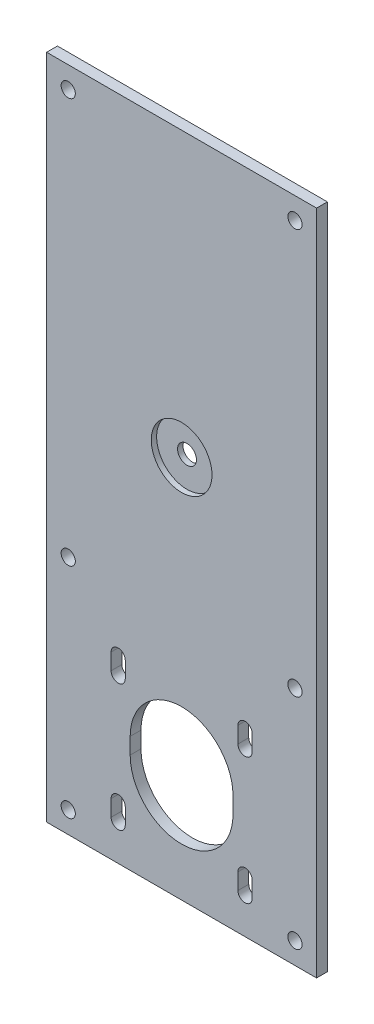
SolidWorks part; units mm, degrees
ref_plane "Front Plane" through (0, 0, 0) normal (0, 0, 1) x (1, 0, 0)
ref_plane "Top Plane" through (0, 0, 0) normal (0, 1, 0) x (1, 0, 0)
ref_plane "Right Plane" through (0, 0, 0) normal (1, 0, 0) x (0, 0, -1)
sketch "Sketch1" plane through (0, 0, 0) normal (0, 0, 1) x (1, 0, 0)
  line L1 (-50, 123.5) -> (50, 123.5)
  line L2 (-50, 123.5) -> (-50, -123.5)
  line L3 (-50, -123.5) -> (50, -123.5)
  line L4 (50, 123.5) -> (50, -123.5)
  line L5 (-50, 123.5) -> (50, -123.5) construction
  line L6 (-50, -123.5) -> (50, 123.5) construction
  line L8 (-19.05, -80.5) -> (-19.05, -86.5)
  line L9 (19.05, -86.5) -> (19.05, -80.5)
  line L10 (-23.5, -57) -> (-23.5, -63) construction
  line L14 (-20.87, -57) -> (-20.87, -63)
  line L15 (-26.13, -57) -> (-26.13, -63)
  line L16 (0, -83.5) -> (41.1398, -83.5) construction
  line L17 (0, -83.5) -> (0, -119.2312) construction
  line L18 (23.5, -57) -> (23.5, -63) construction
  line L19 (20.87, -57) -> (20.87, -63)
  line L20 (26.13, -57) -> (26.13, -63)
  line L21 (23.5, -110) -> (23.5, -104) construction
  line L22 (20.87, -110) -> (20.87, -104)
  line L23 (26.13, -110) -> (26.13, -104)
  line L24 (-23.5, -110) -> (-23.5, -104) construction
  line L25 (-20.87, -110) -> (-20.87, -104)
  line L26 (-26.13, -110) -> (-26.13, -104)
  circle A0 centre (-42, -34.5) radius 2.625
  circle A1 centre (42, -34.5) radius 2.625
  circle A2 centre (-42, -115.5) radius 2.625
  circle A3 centre (42, -115.5) radius 2.625
  arc A6 (19.05, -80.5) -> (-19.05, -80.5) centre (0, -80.5) ccw
  arc A7 (-19.05, -86.5) -> (19.05, -86.5) centre (0, -86.5) ccw
  arc A10 (-20.87, -57) -> (-26.13, -57) centre (-23.5, -57) ccw
  arc A11 (-26.13, -63) -> (-20.87, -63) centre (-23.5, -63) ccw
  arc A12 (20.87, -57) -> (26.13, -57) centre (23.5, -57) cw
  arc A13 (26.13, -63) -> (20.87, -63) centre (23.5, -63) cw
  arc A14 (20.87, -110) -> (26.13, -110) centre (23.5, -110) ccw
  arc A15 (26.13, -104) -> (20.87, -104) centre (23.5, -104) ccw
  arc A16 (-20.87, -110) -> (-26.13, -110) centre (-23.5, -110) cw
  arc A17 (-26.13, -104) -> (-20.87, -104) centre (-23.5, -104) cw
  circle A18 centre (0, 18.5) radius 3.5
  circle A19 centre (42, 115.5) radius 2.625
  circle A20 centre (-42, 115.5) radius 2.625
  circle A21 centre (-14, 32.5) radius 2.625 construction
  circle A22 centre (14, 32.5) radius 2.625 construction
  circle A23 centre (14, 4.5) radius 2.625 construction
  circle A24 centre (-14, 4.5) radius 2.625 construction
  point P0 (0, 0)
  point P14 (-23.5, -60)
  point P17 (0, -83.5)
  point P34 (23.5, -60)
  point P41 (23.5, -107)
  point P48 (-23.5, -107)
  dimension "D3" = 5.25
  dimension "D4" = 81
  dimension "D6" = 5.26
  dimension "D8" = 8
  dimension "D12" = 19.05
  dimension "D14" = 3
  dimension "D15" = 23.5
  dimension "D16" = 7
  dimension "D19" = 5.25
  dimension "D1" = 100
  dimension "D2" = 247
  dimension "D5" = 84
  dimension "D7" = 6
  dimension "D9" = 6
  dimension "D10" = 8
  dimension "D11" = 23.5
  dimension "D17" = 105
  dimension "D18" = 8
  dimension "D20" = 28
  dimension "D21" = 28
  dimension "D22" = 14
  dimension "D23" = 14
  dimension "D24" = 83.5
extrude "Boss-Extrude1" add sketch "Sketch1" along normal blind 4
sketch "Sketch2" plane through (0, 0, 4) normal (0, 0, 1) x (1, 0, 0)
  circle A0 centre (0, 18.5) radius 11.25
  dimension "D1" = 22.5
extrude "Cut-Extrude1" cut sketch "Sketch2" against normal blind 2
